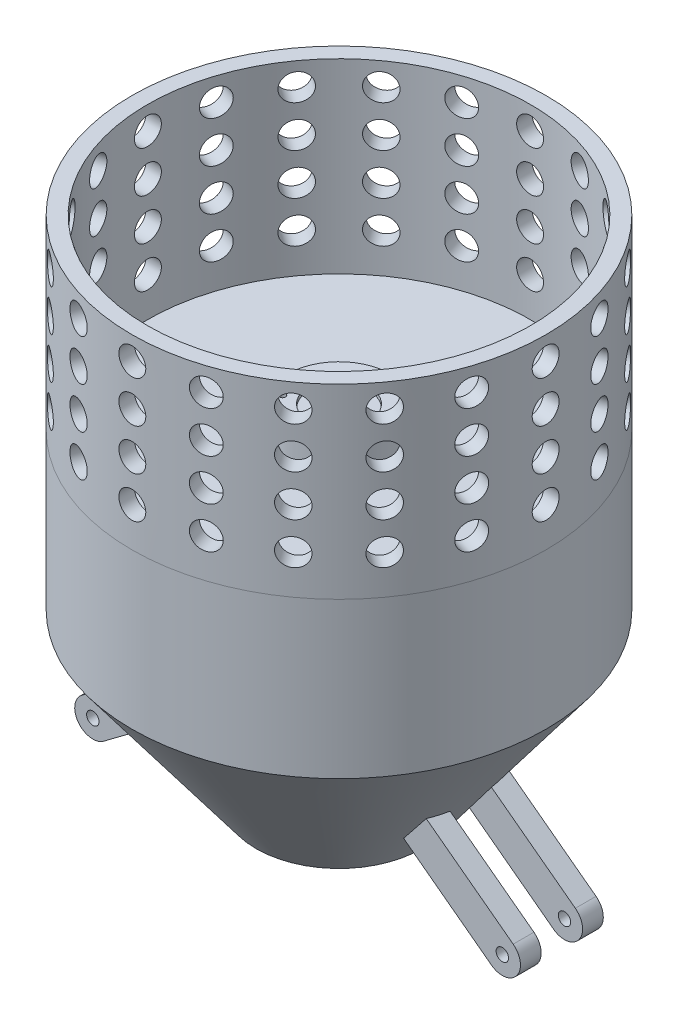
SolidWorks part; units mm, degrees
ref_plane "Front Plane" through (0, 0, 0) normal (0, 0, 1) x (1, 0, 0)
ref_plane "Top Plane" through (0, 0, 0) normal (0, 1, 0) x (1, 0, 0)
ref_plane "Right Plane" through (0, 0, 0) normal (1, 0, 0) x (0, 0, -1)
sketch "Sketch2" plane through (0, 0, 0) normal (0, 0, 1) x (1, 0, 0)
  line L0 (0, 57.3493) -> (0, -66.5497) construction
  line L1 (0, 55.2295) -> (-200, 55.2295)
  line L2 (-200, 55.2295) -> (-200, -94.7705)
  line L3 (-200, -94.7705) -> (-80, -254.7705)
  line L4 (-80, -254.7705) -> (-60, -254.7705)
  line L5 (-60, -254.7705) -> (-180, -94.7705)
  line L6 (-180, -94.7705) -> (-180, 35.2295)
  line L7 (-180, 35.2295) -> (-97.5, 35.2295)
  line L8 (0, 25.2295) -> (0, 55.2295)
  line L9 (-97.5, 35.2295) -> (-97.5, -104.7705)
  line L10 (-97.5, -104.7705) -> (-35, -176.1496)
  line L11 (-35, -176.1496) -> (0, -176.1496)
  line L12 (0, -176.1496) -> (0, 25.2295)
  dimension "D1" = 20
  dimension "D2" = 200
  dimension "D3" = 20
  dimension "D4" = 20
  dimension "D5" = 150
  dimension "D6" = 160
  dimension "D7" = 97.5
  dimension "D8" = 35
  dimension "D9" = 82.5
  dimension "D10" = 80
revolve "Revolve1" add sketch "Sketch2" angle 360 about L0
sketch "Sketch3" plane through (0, 0, 0) normal (0, 0, 1) x (1, 0, 0)
  line L0 (0, 80.7285) -> (0, -227.5722) construction
  line L1 (-97.5, 35.2295) -> (180, 35.2295) construction
  line L2 (-180, 35.2295) -> (180, 35.2295) construction
  circle A16 centre (-107.8608, 4.2503) radius 12.5
  circle A17 centre (-107.8608, -9.7358) radius 12.5
  circle A18 centre (-107.8608, -23.722) radius 12.5
  circle A19 centre (-107.8608, -37.7081) radius 12.5
  circle A20 centre (-107.8608, -51.6942) radius 12.5
  circle A21 centre (-107.8608, -65.6804) radius 12.5
  circle A22 centre (-107.8608, -79.6665) radius 12.5
  circle A23 centre (-107.8608, -93.6526) radius 12.5
  dimension "D2" = 25
  dimension "D1" = 97.5
revolve "Cut-Revolve1" cut sketch "Sketch3" angle 360 about L0
sketch "Sketch4" plane through (0, 0, 0) normal (0, 0, 1) x (1, 0, 0)
  line L2 (0, 86.0646) -> (0, -290.0279) construction
  circle A0 centre (-99.4467, -117.118) radius 12.5
  circle A1 centre (-89.4415, -133.1263) radius 12.5
  circle A2 centre (-79.4363, -149.1347) radius 12.5
  circle A3 centre (-69.431, -165.143) radius 12.5
  circle A4 centre (-59.4258, -181.1514) radius 12.5
  circle A5 centre (-49.4206, -197.1597) radius 12.5
  dimension "D1" = 25
revolve "Cut-Revolve2" cut sketch "Sketch4" angle 360 about L2
sketch "Sketch5" plane through (0, 55.2295, 0) normal (0, 1, 0) x (1, 0, 0)
  line L0 (-5.5226, 5.7879) -> (5.0522, 6.2028)
  line L2 (5.5226, -5.7879) -> (-5.0522, -6.2028)
  circle A0 centre (0, 0) radius 50
  arc A1 (-5.5226, 5.7879) -> (-5.0522, -6.2028) centre (0, 0) ccw
  arc A2 (5.5226, -5.7879) -> (5.0522, 6.2028) centre (0, 0) ccw
  dimension "D1" = 100
extrude "Boss-Extrude1" add sketch "Sketch5" along normal blind 22
sketch "Sketch8" plane through (0, 0, 0) normal (0, 0, 1) x (1, 0, 0)
  line L0 (0, 134.6652) -> (0, -262.2129) construction
  line L1 (0, 35.2295) -> (-139.6326, 35.2295)
  line L2 (-97.5, 35.2295) -> (97.5, 35.2295) construction
  line L3 (-180, 35.2295) -> (180, 35.2295) construction
  line L4 (-139.6326, 35.2295) -> (-139.6326, -94.7705)
  line L5 (180, -94.7705) -> (-180, -94.7705) construction
  line L6 (-139.6326, -94.7705) -> (-77.993, -221.3072)
  line L7 (-77.993, -221.3072) -> (0, -221.3072)
  line L8 (0, -221.3072) -> (0, 35.2295)
revolve "Cut-Revolve3" cut sketch "Sketch8" angle 360 about L0
sketch "Sketch9" plane through (0, 0, 0) normal (0, 0, 1) x (1, 0, 0)
  line L0 (0, 118.4935) -> (0, -227.665) construction
  line L1 (0, 55.2295) -> (20, 55.2295)
  line L2 (50, 55.2295) -> (-50, 55.2295) construction
  line L3 (20, 55.2295) -> (20, -4.5556)
  line L4 (20, -4.5556) -> (0, -4.5556)
  line L5 (0, -4.5556) -> (0, 55.2295)
  dimension "D1" = 20
revolve "Cut-Revolve4" cut sketch "Sketch9" angle 360 about L0
sketch "Sketch10" plane through (0, 55.2295, 0) normal (0, -1, 0) x (1, 0, 0)
  circle A0 centre (0, 0) radius 20
  circle A1 centre (0, 0) radius 8
extrude "Boss-Extrude2" add sketch "Sketch10" along normal blind 10
sketch "Sketch12" plane through (0, 0, 0) normal (1, 0, 0) x (0, 0, -1)
  line L0 (0, 111.458) -> (0, -53.1613) construction
  line L1 (0, 78.126) -> (-17.5, 78.126)
  line L2 (-17.5, 78.126) -> (-17.5, 14.183)
  line L3 (-17.5, 14.183) -> (0, 14.183)
  line L4 (0, 14.183) -> (0, 78.126)
  dimension "D1" = 35
sketch "Sketch13" plane through (0, 77.2295, 0) normal (0, 1, 0) x (1, 0, 0)
  circle A0 centre (0, 0) radius 17.5
  dimension "D1" = 35
extrude "Cut-Extrude2" cut sketch "Sketch13" against normal blind 136
sketch "Sketch14" plane through (0, 77.2295, 0) normal (0, 1, 0) x (1, 0, 0)
  circle A0 centre (0, 0) radius 29
  dimension "D1" = 58
extrude "Cut-Extrude3" cut sketch "Sketch14" against normal blind 3.5
sketch "Sketch15" plane through (0, 73.7295, 0) normal (0, 1, 0) x (1, 0, 0)
  circle A0 centre (0, 0) radius 40 construction
  circle A1 centre (0, 40) radius 2.5
  dimension "D1" = 80
  dimension "D2" = 5
extrude "Cut-Extrude4" cut sketch "Sketch15" against normal blind 3.5
sketch "Sketch16" plane through (0, 77.2295, 0) normal (0, 1, 0) x (1, 0, 0)
  circle A0 centre (0, 0) radius 40 construction
  circle A1 centre (0, 40) radius 3
  circle A2 centre (34.641, -20) radius 3
  circle A3 centre (-34.641, -20) radius 3
  point P11 (0, 0)
  dimension "D1" = 80
  dimension "D2" = 6
  dimension "D3" = 3
extrude "Cut-Extrude5" cut sketch "Sketch16" against normal blind 11.5
sketch "Sketch17" plane through (0, 55.2295, 0) normal (0, 1, 0) x (1, 0, 0)
  circle A0 centre (0, 0) radius 200
  circle A1 centre (0, 0) radius 185
  dimension "D1" = 15
  dimension "D2" = 400
extrude "Boss-Extrude3" add sketch "Sketch17" along normal blind 180 separate body
sketch "Sketch18" plane through (0, 0, 0) normal (0, 0, 1) x (1, 0, 0)
  circle A0 centre (0, 213.0026) radius 12.9812
  circle A1 centre (0, 173.0026) radius 12.9812
  circle A2 centre (0, 133.0026) radius 12.9812
  circle A3 centre (0, 93.0026) radius 12.9812
  dimension "D1" = 4
extrude "Cut-Extrude6" cut sketch "Sketch18" against normal through all
pattern_circular "CirPattern5" count 20 over 360 about axis through (0, 235.2295, 0) along (0, -1, 0) of "Cut-Extrude6"
ref_plane "Plane1" through (0, 0, 30) normal (0, 0, 1) x (1, 0, 0)
ref_plane "Plane2" through (0, 0, -30) normal (0, 0, 1) x (1, 0, 0)
sketch "Sketch19" plane through (0, 0, 30) normal (0, 0, 1) x (1, 0, 0)
  line L0 (-128.2476, -190.4404) -> (-208.2476, -250.4404)
  line L1 (-200, -94.7705) -> (-80, -254.7705) construction
  line L2 (-217.5378, -279.283) -> (-117.7476, -204.4404) construction
  line L3 (-107.2476, -218.4404) -> (-128.2476, -190.4404)
  line L4 (0, 330.9422) -> (0, -514.2371) construction
  line L5 (-128.2476, -350.4358) -> (-46.7488, -350.4358) construction
  line L6 (-107.2476, -218.4404) -> (-187.2476, -278.4404)
  line L7 (-142.5247, -297.1204) -> (-142.5247, -298.0668)
  line L8 (-213.658, -202.276) -> (-214.5665, -202.011)
  line L9 (-128.2476, -190.4404) -> (-208.2476, -250.4404)
  line L10 (-46.7488, -350.4358) -> (-46.7488, -315.0874) construction
  line L11 (-116.9923, -315.4358) -> (-81.7488, -315.4358) construction
  line L12 (-81.7488, -315.4358) -> (-81.7488, -315.0874) construction
  line L14 (-128.2476, -190.4404) -> (-177.5247, -227.3982) construction
  line L15 (-107.2476, -218.4404) -> (-142.5247, -244.8982) construction
  line L16 (-177.5247, -227.3982) -> (-177.5247, -315.0874) construction
  line L17 (-142.5247, -244.8982) -> (-142.5247, -297.1204) construction
  line L18 (-177.5247, -315.0874) -> (-128.2476, -350.4358) construction
  line L19 (-142.5247, -297.1204) -> (-116.9923, -315.4358) construction
  line L20 (-107.2476, -218.4404) -> (-187.2476, -278.4404)
  line L21 (217.5378, -279.283) -> (117.7476, -204.4404) construction
  line L22 (107.2476, -218.4404) -> (187.2476, -278.4404)
  line L23 (128.2476, -190.4404) -> (208.2476, -250.4404)
  line L24 (213.658, -202.276) -> (214.5665, -202.011)
  line L25 (142.5247, -297.1204) -> (142.5247, -298.0668)
  line L26 (107.2476, -218.4404) -> (187.2476, -278.4404)
  line L27 (107.2476, -218.4404) -> (128.2476, -190.4404)
  line L28 (128.2476, -190.4404) -> (208.2476, -250.4404)
  arc A3 (-208.2476, -250.4404) -> (-187.2476, -278.4404) centre (-197.7476, -264.4404) ccw
  circle A4 centre (-197.7476, -264.4404) radius 6
  circle A5 centre (197.7476, -264.4404) radius 6
  arc A6 (208.2476, -250.4404) -> (187.2476, -278.4404) centre (197.7476, -264.4404) cw
  dimension "D2" = 100
  dimension "D3" = 12
  dimension "D1" = 35
extrude "Boss-Extrude4" add sketch "Sketch19" along normal mid plane 20 separate body contours L0 A3 L6 L3 A4 | A6 L23 L27 L22 A5
sketch "Sketch20" plane through (-173.4898, -130.1174, 0) normal (0.8, 0.6, 0) x (0, 0, -1)
  line L4 (-20, -110.4037) -> (-20, -75.4037)
  line L5 (-20, -75.4037) -> (-40, -75.4037)
  line L6 (-40, -75.4037) -> (-40, -110.4037)
  line L7 (-40, -110.4037) -> (-20, -110.4037)
  line L8 (-20, -110.4037) -> (-20, -75.4037)
  line L9 (-20, -75.4037) -> (-40, -75.4037)
  line L10 (-40, -75.4037) -> (-40, -110.4037)
  line L11 (-40, -110.4037) -> (-20, -110.4037)
  dimension "D1" = 0
extrude "Boss-Extrude5" add sketch "Sketch20" along normal up to surface (5.0248 mm away)
sketch "Sketch21" plane through (0, 0, -30) normal (0, 0, 1) x (1, 0, 0)
  line L0 (-137.3728, -197.2843) -> (-116.3728, -225.2843)
  line L1 (0, 306.261) -> (0, -425.2331) construction
  line L2 (-127.2478, -189.6905) -> (-208.2476, -250.4404)
  line L3 (-187.2476, -278.4404) -> (-106.0512, -217.5431)
  line L4 (-137.3728, -197.2843) -> (-208.2476, -250.4404)
  line L5 (-187.2476, -278.4404) -> (-116.3728, -225.2843)
  line L6 (187.2476, -278.4404) -> (116.3728, -225.2843)
  line L7 (137.3728, -197.2843) -> (208.2476, -250.4404)
  line L8 (137.3728, -197.2843) -> (116.3728, -225.2843)
  circle A0 centre (-197.7476, -264.4404) radius 6
  arc A1 (-208.2476, -250.4404) -> (-187.2476, -278.4404) centre (-197.7476, -264.4404) ccw
  arc A2 (-208.2476, -250.4404) -> (-187.2476, -278.4404) centre (-197.7476, -264.4404) ccw
  arc A3 (208.2476, -250.4404) -> (187.2476, -278.4404) centre (197.7476, -264.4404) cw
  circle A4 centre (197.7476, -264.4404) radius 6
  spline S1 degree 3 poles (658.5124, -862.0911) (-75.9643, -582.2762) (-182.3695, 171.9012) (-847.2442, 504.2842) knots -27.860286 -27.860286 -27.860286 -27.860286 29.219747 29.219747 29.219747 29.219747 only from (-106.0512, -217.5431) to (-127.2478, -189.6905)
  dimension "D1" = 0
extrude "Boss-Extrude6" add sketch "Sketch21" along normal mid plane 20 separate body
sketch "Sketch23" plane through (-182.6151, -136.9613, 0) normal (0.8, 0.6, 0) x (0, 0, -1)
  line L1 (40, -75.4037) -> (20, -75.4037)
  line L2 (40, -75.4037) -> (40, -110.4037)
  line L3 (40, -110.4037) -> (20, -110.4037)
  line L4 (20, -75.4037) -> (20, -110.4037)
extrude "Boss-Extrude7" add sketch "Sketch23" along normal up to surface (16.4313 mm away)
sketch "Sketch24" plane through (182.6151, -136.9613, 0) normal (-0.8, 0.6, 0) x (0, 0, 1)
  line L1 (-40, -75.4037) -> (-20, -75.4037)
  line L2 (-40, -75.4037) -> (-40, -110.4037)
  line L3 (-40, -110.4037) -> (-20, -110.4037)
  line L4 (-20, -75.4037) -> (-20, -110.4037)
extrude "Boss-Extrude8" add sketch "Sketch24" along normal blind 20
sketch "Sketch25" plane through (173.4898, -130.1174, 0) normal (-0.8, 0.6, 0) x (0, 0, 1)
  line L1 (40, -75.4037) -> (20, -75.4037)
  line L2 (40, -75.4037) -> (40, -110.4037)
  line L3 (40, -110.4037) -> (20, -110.4037)
  line L4 (20, -75.4037) -> (20, -110.4037)
extrude "Boss-Extrude9" add sketch "Sketch25" along normal up to surface (5.0248 mm away)
